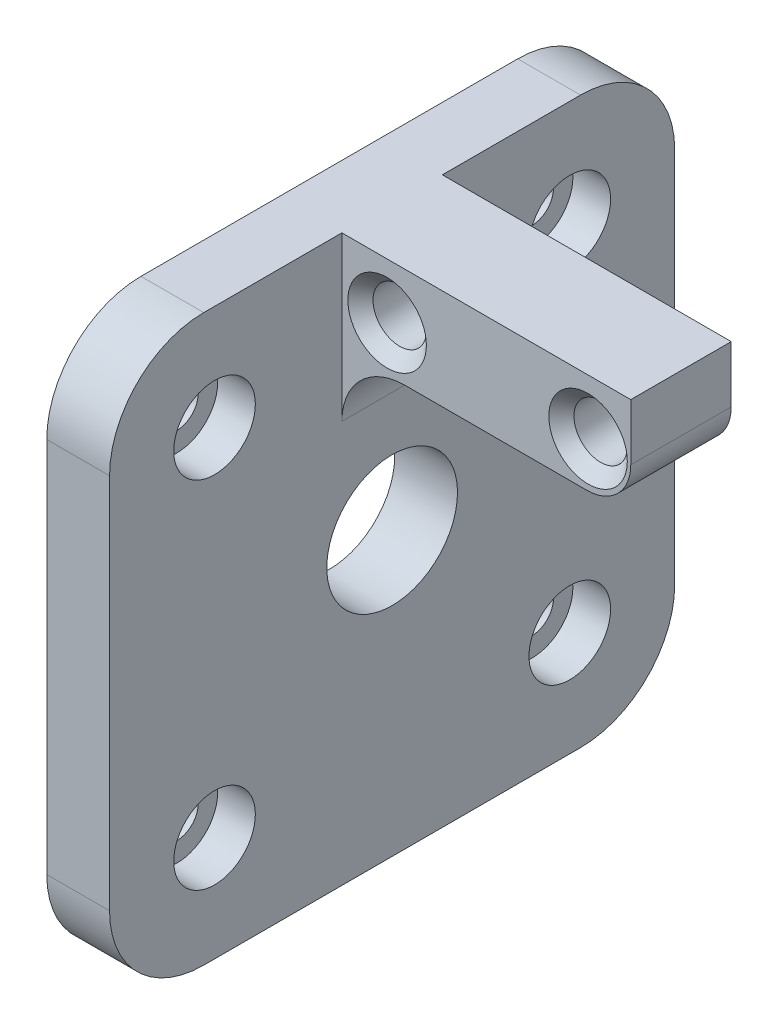
SolidWorks part; units mm, degrees
ref_plane "Front Plane" through (0, 0, 0) normal (0, 0, 1) x (1, 0, 0)
ref_plane "Top Plane" through (0, 0, 0) normal (0, 1, 0) x (1, 0, 0)
ref_plane "Right Plane" through (0, 0, 0) normal (1, 0, 0) x (0, 0, -1)
sketch "Sketch1" plane through (0, 0, 0) normal (1, 0, 0) x (0, 0, -1)
  line L1 (-22.5, -22.5) -> (22.5, -22.5)
  line L2 (-22.5, -22.5) -> (-22.5, 22.5)
  line L3 (-22.5, 22.5) -> (22.5, 22.5)
  line L4 (22.5, -22.5) -> (22.5, 22.5)
  line L5 (-22.5, -22.5) -> (22.5, 22.5) construction
  line L6 (-22.5, 22.5) -> (22.5, -22.5) construction
  line L7 (-4, 22.5) -> (4, 22.5)
  line L8 (-4, 22.5) -> (-4, 14.5)
  line L9 (-4, 14.5) -> (4, 14.5)
  line L10 (4, 22.5) -> (4, 14.5)
  circle A0 centre (0, 0) radius 5.205
  circle A1 centre (0, 0) radius 20 construction
  point P12 (0, 22.5)
  point P15 (0, 14.5)
  dimension "D1" = 10.41
  dimension "D4" = 40
  dimension "D2" = 8
  dimension "D3" = 45
  dimension "D5" = 8
extrude "Boss-Extrude1" add sketch "Sketch1" along normal blind 5 contours L3 L10 L9 L8 L2 L1 L4 A0 | L10 L3 L8 L9 region at (0, 0, 21.8636) region at (0, 18.5, 0)
extrude "Boss-Extrude2" add sketch "Sketch1<3>" along normal blind 28 contours L10 L3 L8 L9 region at (0, 18.5, 0)
sketch "Sketch1<3>" plane through (0, 0, 0) normal (1, 0, 0) x (0, 0, -1) same geometry as "Sketch1"
fillet "Fillet1" radius 7.5 4 edges at (2.5, -22.5, 22.5) (2.5, -22.5, -22.5) (2.5, 22.5, -22.5) (2.5, 22.5, 22.5)
fillet "Fillet2" radius 5 1 edges at (5, 14.5, 0)
fillet "Fillet3" radius 3.5 1 edges at (28, 14.5, 0)
sketch "Sketch2" plane through (0, 0, 0) normal (0, 0, 1) x (1, 0, 0)
  circle A0 centre (24.6, 18.1) radius 3.1 construction
  circle A1 centre (8.6, 18.1) radius 3.1
  circle A2 centre (8.6, 18.1) radius 3.1 construction
  circle A3 centre (24.6, 18.1) radius 3.1 construction
  circle A4 centre (8.6, 18.1) radius 2.125
  circle A5 centre (24.6, 18.1) radius 2.125
  dimension "D2" = 4.25
  dimension "D3" = 4.25
  dimension "D4" = 16
  dimension "D1" = 0
extrude "Cut-Extrude1" cut sketch "Sketch2" against normal through all both and the other way through all
hole_wizard "CBORE for M3 SHCS1" positions "Sketch5" profile "Sketch7" counterbore size "M3" standard "ANSI Metric" end condition through all
sketch "Sketch5" plane through (5, 0, 0) normal (1, 0, 0) x (0, 0, -1)
  line L0 (-22.5, 22.5) -> (22.5, -22.5) construction
  line L1 (-22.5, -22.5) -> (22.5, 22.5) construction
  circle A0 centre (0, 0) radius 20 construction
  point P0 (-14.1421, 14.1421)
  point P6 (14.1421, 14.1421)
  point P10 (-14.1421, -14.1421)
  point P12 (14.1421, -14.1421)
sketch "Sketch7" plane through (5, 14.1421, 14.1421) normal (0, 1, 0) x (0, 0, -1)
  line L0 (0, 0) -> (0, 5)
  line L1 (0, 5) -> (1.7, 5)
  line L3 (1.7, 5) -> (1.7, 3)
  line L4 (1.7, 3) -> (3.25, 3)
  line L5 (3.25, 3) -> (3.25, 0)
  line L7 (3.25, 0) -> (0, 0)
  line L11 (0, -6.35) -> (0, 107.95) construction
  dimension "Thru Hole Dia." = 3.4
  dimension "Thru Hole Depth" = 5
  dimension "C'Bore Dia." = 6.5
  dimension "C'Bore Depth" = 3
chamfer "Chamfer1" distance 1 angle 45 2 edges at (24.6, 20.225, 4) (8.6, 20.225, 4)
